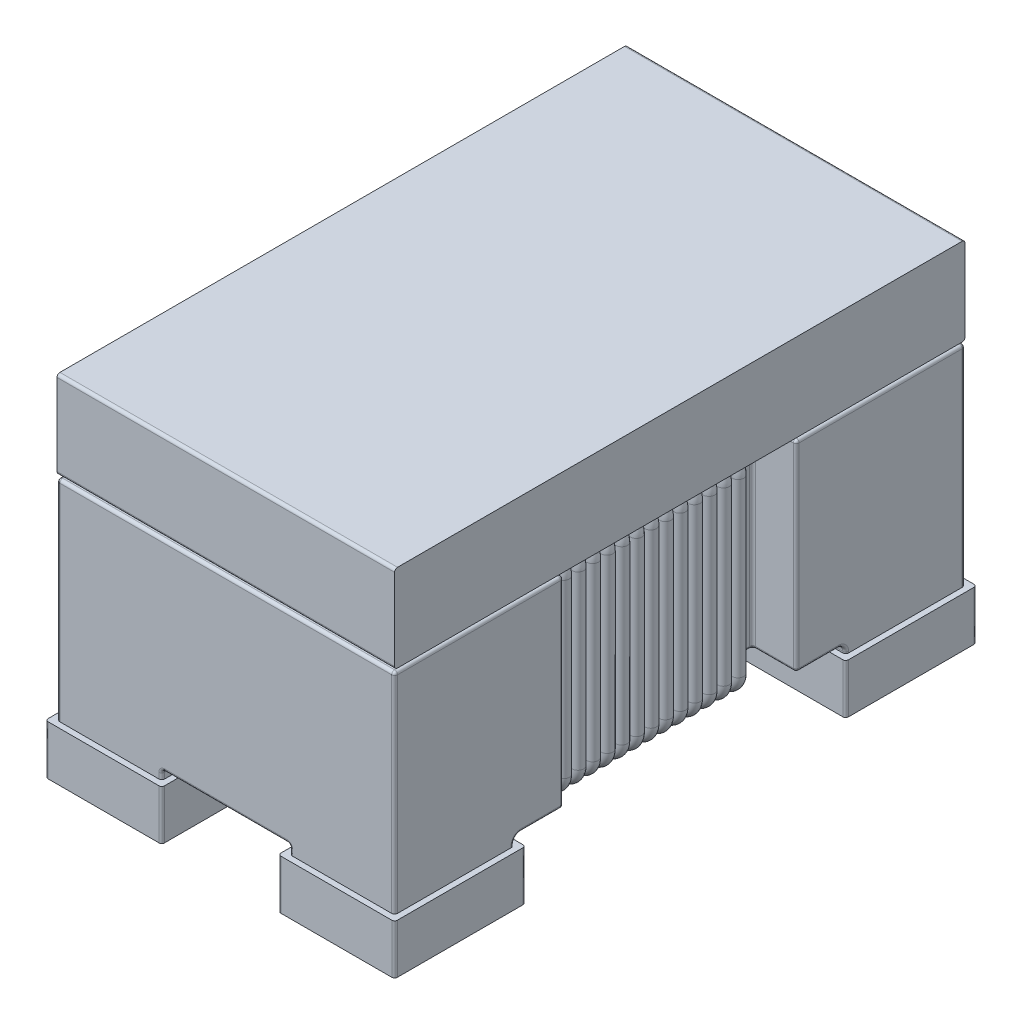
SolidWorks part; units mm, degrees
ref_plane "Plano frontal" through (0, 0, 0) normal (0, 0, 1) x (1, 0, 0)
ref_plane "Plano superior" through (0, 0, 0) normal (0, 1, 0) x (1, 0, 0)
ref_plane "Plano direito" through (0, 0, 0) normal (1, 0, 0) x (0, 0, -1)
sketch "Esboço1" plane through (0, 0, 0) normal (1, 0, 0) x (0, 0, -1)
  line L0 (0, 0) -> (0, 1.6247) construction
  line L1 (0.545, 0.2) -> (-0.545, 0.2)
  line L2 (-0.57, 0.175) -> (-0.57, 0)
  line L3 (-0.57, 0) -> (-0.98, 0)
  line L4 (-0.98, 0) -> (-0.98, 0.88)
  line L5 (-0.97, 0.89) -> (-0.41, 0.89)
  line L6 (0.97, 0.9) -> (-0.97, 0.9)
  line L7 (-0.98, 0.91) -> (-0.98, 1.19)
  line L8 (-0.97, 1.2) -> (0.97, 1.2)
  line L9 (-0.98, 0.17) -> (-0.57, 0.17) construction
  line L10 (0.39, 0.79) -> (-0.39, 0.79)
  line L11 (-0.4, 0.8) -> (-0.4, 0.88)
  line L12 (0.4, 0.8) -> (0.4, 0.88)
  line L13 (0.98, 0.91) -> (0.98, 1.19)
  line L14 (0.97, 0.89) -> (0.41, 0.89)
  line L15 (0.98, 0) -> (0.98, 0.88)
  line L16 (0.57, 0) -> (0.98, 0)
  line L17 (0.57, 0.175) -> (0.57, 0)
  arc A0 (-0.545, 0.2) -> (-0.57, 0.175) centre (-0.545, 0.175) ccw
  arc A1 (-0.39, 0.79) -> (-0.4, 0.8) centre (-0.39, 0.8) cw
  arc A2 (-0.4, 0.88) -> (-0.41, 0.89) centre (-0.41, 0.88) ccw
  arc A3 (-0.98, 0.88) -> (-0.97, 0.89) centre (-0.97, 0.88) cw
  arc A4 (-0.97, 0.9) -> (-0.98, 0.91) centre (-0.97, 0.91) cw
  arc A5 (-0.98, 1.19) -> (-0.97, 1.2) centre (-0.97, 1.19) cw
  arc A6 (0.98, 1.19) -> (0.97, 1.2) centre (0.97, 1.19) ccw
  arc A7 (0.97, 0.9) -> (0.98, 0.91) centre (0.97, 0.91) ccw
  arc A8 (0.98, 0.88) -> (0.97, 0.89) centre (0.97, 0.88) ccw
  arc A9 (0.4, 0.88) -> (0.41, 0.89) centre (0.41, 0.88) cw
  arc A10 (0.39, 0.79) -> (0.4, 0.8) centre (0.39, 0.8) ccw
  arc A11 (0.545, 0.2) -> (0.57, 0.175) centre (0.545, 0.175) cw
  point P3 (0.98, 1.2)
  point P14 (0, 0.9)
  point P18 (-0.57, 0.2)
  point P19 (0, 1.2)
  point P29 (-0.98, 0.9)
  point P32 (-0.98, 1.2)
  point P50 (0, 0.79)
  point P52 (0, 0.2)
  point P53 (0.98, 0.9)
  point P54 (0.57, 0.2)
  dimension "D8" = 0.025
  dimension "D11" = 0.01
  dimension "D1" = 0.98
  dimension "D2" = 0.41
  dimension "D3" = 0.01
  dimension "D4" = 0.2
  dimension "D5" = 1.2
  dimension "D6" = 0.3
  dimension "D7" = 0.17
  dimension "D9" = 0.4
  dimension "D10" = 0.1
extrude "Ressalto-extrusão1" add sketch "Esboço1" along normal blind 0.58 and the other way blind 0.58
sketch "Esboço2" plane through (0, 0, -0.98) normal (0, 0, -1) x (-1, 0, 0)
  line L0 (0, 0) -> (0, 0.7328) construction
  line L1 (0.58, 0) -> (-0.58, 0) construction
  line L2 (-0.22, 0.2) -> (0.22, 0.2)
  line L3 (-0.22, 0.2) -> (-0.22, 0)
  line L4 (-0.22, 0) -> (0.22, 0)
  line L5 (0.22, 0.2) -> (0.22, 0)
  line L6 (-0.22, 0.2) -> (0.22, 0) construction
  line L7 (-0.22, 0) -> (0.22, 0.2) construction
  line L8 (-0.58, 0) -> (-0.58, 0.88) construction
  point P3 (0, 0.1)
  dimension "D1" = 0.2
  dimension "D2" = 0.36
extrude "Corte-extrusão1" cut sketch "Esboço2" against normal through all
sketch "Esboço3" plane through (0, 0.79, 0) normal (0, 1, 0) x (1, 0, 0)
  line L0 (-0.58, -0.4) -> (0.58, -0.4) construction
  line L1 (0.58, 0.4) -> (0.43, 0.4)
  line L2 (0.58, 0.4) -> (0.58, -0.4)
  line L3 (0.58, -0.4) -> (0.43, -0.4)
  line L4 (0.43, 0.4) -> (0.43, -0.4)
  line L5 (0, 0) -> (0, 0.6313) construction
  line L6 (-0.43, 0.4) -> (-0.43, -0.4)
  line L7 (-0.58, -0.4) -> (-0.43, -0.4)
  line L8 (-0.58, 0.4) -> (-0.58, -0.4)
  line L9 (-0.58, 0.4) -> (-0.43, 0.4)
  dimension "D1" = 0.15
extrude "Corte-extrusão2" cut sketch "Esboço3" against normal up to next (0.59 mm away) and the other way blind 0.02
fillet "Filete1" radius 0.01 36 edges at (0.58, 0.2, 0.4725) (0.58, 0.1927, 0.5627) (0.58, 0.0875, 0.57) (0.58, 0, 0.775) (0.58, 0.44, 0.98) (0.58, 0.8871, 0.9771) (0.58, 0.89, 0.69) (0.58, 0.8871, 0.4029) (0.58, 0.54, 0.4) (0.58, 0.8871, -0.4029) (0.58, 0.89, -0.69) (0.58, 0.8871, -0.9771) (0.58, 0.44, -0.98) (0.58, 0, -0.775) (0.58, 0.0875, -0.57) (0.58, 0.1927, -0.5627) (0.58, 0.2, -0.4725) (0.58, 0.54, -0.4) (-0.58, 0.54, 0.4) (-0.58, 0.8871, 0.4029) (-0.58, 0.89, 0.69) (-0.58, 0.8871, 0.9771) (-0.58, 0.44, 0.98) (-0.58, 0, 0.775) (-0.58, 0.0875, 0.57) (-0.58, 0.1927, 0.5627) (-0.58, 0.2, 0.4725) (-0.58, 0.1927, -0.5627) (-0.58, 0.0875, -0.57) (-0.58, 0, -0.775) (-0.58, 0.44, -0.98) (-0.58, 0.8871, -0.9771) (-0.58, 0.89, -0.69) (-0.58, 0.8871, -0.4029) (-0.58, 0.54, -0.4) (-0.58, 0.2, -0.4725)
fillet "Filete2" radius 0.01 30 edges at (0.22, 0.1, -0.98) (-0.22, 0.1, -0.98) (-0.22, 0.1, 0.98) (0.22, 0.1, 0.98) (0.5771, 0.2029, -0.4029) (-0.5771, 0.2029, -0.4029) (-0.5771, 0.2029, 0.4029) (0.5771, 0.2029, 0.4029) (0.5, 0.2, -0.4) (0.22, 0.2, -0.7625) (0, 0.2, -0.98) (-0.22, 0.2, -0.7625) (-0.5, 0.2, -0.4) (-0.5, 0.2, 0.4) (-0.22, 0.2, 0.7625) (0, 0.2, 0.98) (0.22, 0.2, 0.7625) (0.5, 0.2, 0.4) (0.43, 0.7929, 0.3971) (0.43, 0.79, 0) (0.43, 0.7929, -0.3971) (0.43, 0.5, -0.4) (0.43, 0.2, 0) (0.43, 0.5, 0.4) (-0.43, 0.7929, 0.3971) (-0.43, 0.5, 0.4) (-0.43, 0.2, 0) (-0.43, 0.5, -0.4) (-0.43, 0.7929, -0.3971) (-0.43, 0.79, 0)
sketch "Esboço4" plane through (0, 0, 0) normal (0, -1, 0) x (1, 0, 0)
  line L0 (0.6, -1) -> (0.2, -0.55) construction
  line L1 (-0.4, -0.98) -> (-0.4, -0.57) construction
  line L2 (0.6, -0.55) -> (0.2, -1) construction
  line L3 (0.57, -0.775) -> (0.22, -0.775) construction
  line L4 (-0.57, -0.98) -> (-0.23, -0.98) construction
  line L5 (-0.57, -0.57) -> (-0.22, -0.57) construction
  line L6 (-0.57, -0.775) -> (-0.22, -0.775) construction
  line L7 (-0.57, -0.57) -> (-0.57, -0.98) construction
  line L8 (-0.22, -0.57) -> (-0.22, -0.97) construction
  line L9 (0, -0.97) -> (0, 0.97) construction
  line L10 (-0.5906, -0.55) -> (-0.2094, -0.55)
  line L11 (-0.6, -0.5594) -> (-0.6, -0.9906)
  line L12 (-0.5906, -1) -> (-0.2094, -1)
  line L13 (-0.2, -0.5594) -> (-0.2, -0.9906)
  line L14 (-0.6, -0.55) -> (-0.2, -1) construction
  line L15 (-0.6, -1) -> (-0.2, -0.55) construction
  line L16 (-0.21, -0.97) -> (0.21, -0.97) construction
  line L17 (0.21, 0.97) -> (-0.21, 0.97) construction
  line L18 (-0.58, 0) -> (0.58, 0) construction
  line L19 (-0.58, 0.97) -> (-0.58, -0.97) construction
  line L20 (0.58, 0.97) -> (0.58, -0.97) construction
  line L21 (0.4, -0.98) -> (0.4, -0.57) construction
  line L22 (0.2, -0.5594) -> (0.2, -0.9906)
  line L23 (0.5906, -1) -> (0.2094, -1)
  line L24 (0.6, -0.5594) -> (0.6, -0.9906)
  line L25 (0.5906, -0.55) -> (0.2094, -0.55)
  line L26 (0.4, 0.98) -> (0.4, 0.57) construction
  line L27 (-0.6, 1) -> (-0.2, 0.55) construction
  line L28 (-0.6, 0.55) -> (-0.2, 1) construction
  line L29 (-0.57, 0.775) -> (-0.22, 0.775) construction
  line L30 (0.57, 0.775) -> (0.22, 0.775) construction
  line L31 (0.6, 0.55) -> (0.2, 1) construction
  line L32 (-0.4, 0.98) -> (-0.4, 0.57) construction
  line L33 (0.6, 1) -> (0.2, 0.55) construction
  line L34 (0.5906, 0.55) -> (0.2094, 0.55)
  line L35 (0.6, 0.5594) -> (0.6, 0.9906)
  line L36 (0.5906, 1) -> (0.2094, 1)
  line L37 (0.2, 0.5594) -> (0.2, 0.9906)
  line L38 (-0.2, 0.5594) -> (-0.2, 0.9906)
  line L39 (-0.5906, 1) -> (-0.2094, 1)
  line L40 (-0.6, 0.5594) -> (-0.6, 0.9906)
  line L41 (-0.5906, 0.55) -> (-0.2094, 0.55)
  arc A0 (-0.6, -0.9906) -> (-0.5906, -1) centre (-0.5906, -0.9906) ccw
  arc A1 (-0.2094, -1) -> (-0.2, -0.9906) centre (-0.2094, -0.9906) ccw
  arc A2 (-0.2094, -0.55) -> (-0.2, -0.5594) centre (-0.2094, -0.5594) cw
  arc A3 (-0.5906, -0.55) -> (-0.6, -0.5594) centre (-0.5906, -0.5594) ccw
  arc A4 (0.5906, -0.55) -> (0.6, -0.5594) centre (0.5906, -0.5594) cw
  arc A5 (0.2094, -0.55) -> (0.2, -0.5594) centre (0.2094, -0.5594) ccw
  arc A6 (0.2094, -1) -> (0.2, -0.9906) centre (0.2094, -0.9906) cw
  arc A7 (0.6, -0.9906) -> (0.5906, -1) centre (0.5906, -0.9906) cw
  arc A8 (0.6, 0.9906) -> (0.5906, 1) centre (0.5906, 0.9906) ccw
  arc A9 (0.2094, 1) -> (0.2, 0.9906) centre (0.2094, 0.9906) ccw
  arc A10 (0.2094, 0.55) -> (0.2, 0.5594) centre (0.2094, 0.5594) cw
  arc A11 (0.5906, 0.55) -> (0.6, 0.5594) centre (0.5906, 0.5594) ccw
  arc A12 (-0.5906, 0.55) -> (-0.6, 0.5594) centre (-0.5906, 0.5594) cw
  arc A13 (-0.2094, 0.55) -> (-0.2, 0.5594) centre (-0.2094, 0.5594) ccw
  arc A14 (-0.2094, 1) -> (-0.2, 0.9906) centre (-0.2094, 0.9906) cw
  arc A15 (-0.6, 0.9906) -> (-0.5906, 1) centre (-0.5906, 0.9906) cw
  point P13 (-0.4, -0.775)
  point P61 (0.4, -0.775)
  point P102 (0.4, 0.775)
  point P103 (-0.4, 0.775)
  dimension "D3" = 0.0094
  dimension "D2" = 0.45
  dimension "D1" = 0.4
extrude "Ressalto-extrusão2" add sketch "Esboço4" against normal blind 0.17
sketch "Esboço5" plane through (0, 0, -0.4) normal (0, 0, 1) x (1, 0, 0)
  line L0 (0, 0.7922) -> (0, 0.3168) construction
  line L1 (-0.43, 0.495) -> (0.43, 0.495) construction
  line L2 (-0.43, 0.21) -> (-0.43, 0.78) construction
  line L3 (0.43, 0.78) -> (0.43, 0.21) construction
  line L5 (-0.43, 0.84) -> (0.43, 0.84)
  line L6 (-0.48, 0.79) -> (-0.48, 0.2)
  line L7 (-0.43, 0.15) -> (0.43, 0.15)
  line L8 (0.48, 0.79) -> (0.48, 0.2)
  line L9 (-0.48, 0.84) -> (0.48, 0.15) construction
  line L10 (-0.48, 0.15) -> (0.48, 0.84) construction
  line L12 (-0.42, 0.79) -> (0.42, 0.79) construction
  line L13 (0.43, 0.21) -> (0.43, 0.78) construction
  arc A0 (-0.48, 0.2) -> (-0.43, 0.15) centre (-0.43, 0.2) ccw
  arc A1 (0.43, 0.15) -> (0.48, 0.2) centre (0.43, 0.2) ccw
  arc A2 (0.43, 0.84) -> (0.48, 0.79) centre (0.43, 0.79) cw
  arc A3 (-0.43, 0.84) -> (-0.48, 0.79) centre (-0.43, 0.79) ccw
  point P9 (0, 0.495)
  dimension "D3" = 0.05
  dimension "D1" = 0.05
  dimension "D2" = 0.05
sketch "Esboço6" plane through (0, 0, 0) normal (1, 0, 0) x (0, 0, -1)
  line L0 (0.4, 0.495) -> (-0.4958, 0.495) construction
  line L1 (0.4, 0.84) -> (-0.3227, 0.84) construction
  line L2 (0.4, 0.15) -> (0.4, 0.84) construction
  line L3 (0.4, 0.84) -> (0.4, 0.79) construction
  circle A0 centre (0.3, 0.84) radius 0.02
  circle A1 centre (0.25, 0.84) radius 0.02
  circle A2 centre (0.2, 0.84) radius 0.02
  circle A3 centre (0.15, 0.84) radius 0.02
  circle A4 centre (0.1, 0.84) radius 0.02
  circle A5 centre (0.05, 0.84) radius 0.02
  circle A6 centre (0, 0.84) radius 0.02
  circle A7 centre (-0.05, 0.84) radius 0.02
  circle A8 centre (-0.1, 0.84) radius 0.02
  circle A9 centre (-0.15, 0.84) radius 0.02
  circle A10 centre (-0.2, 0.84) radius 0.02
  circle A11 centre (-0.25, 0.84) radius 0.02
  circle A12 centre (-0.3, 0.84) radius 0.02
  dimension "D1" = 0.04
  dimension "D2" = 0.1
  dimension "D3" = 13
sweep "Varredura1" add profiles "Esboço6" path "Esboço5"
